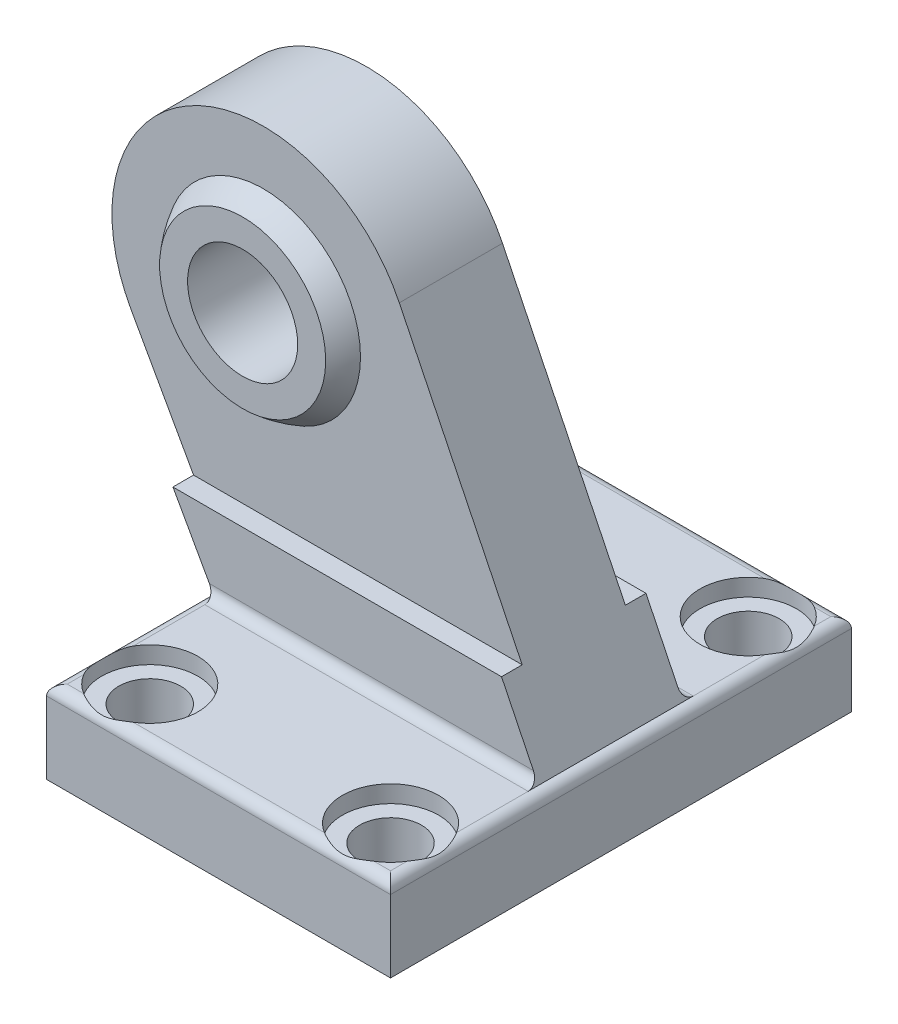
SolidWorks part; units mm, degrees
ref_plane "Front Plane" through (0, 0, 0) normal (0, 0, 1) x (1, 0, 0)
ref_plane "Top Plane" through (0, 0, 0) normal (0, 1, 0) x (1, 0, 0)
ref_plane "Right Plane" through (0, 0, 0) normal (1, 0, 0) x (0, 0, -1)
ref_plane "Plane1" through (0, 0, 0) normal (0, 0, 1) x (1, 0, 0)
sketch "Sketch1" plane through (0, 0, 0) normal (0, 0, 1) x (1, 0, 0)
  line L0 (-38.7147, 39.2858) -> (-23.5, 12)
  line L1 (-25, 10.5) -> (-25, 0)
  line L2 (-25, 0) -> (25, 0)
  line L3 (25, 0) -> (25, 10.5)
  line L4 (23.5, 12) -> (0.2753, 59.6404)
  arc A0 (0.2753, 59.6404) -> (-38.7147, 39.2858) centre (-19.5, 50) ccw
  arc A1 (-23.5, 12) -> (-25, 10.5) centre (-23.5, 10.5) ccw
  arc A2 (25, 10.5) -> (23.5, 12) centre (23.5, 10.5) ccw
extrude "Boss-Extrude1" add sketch "Sketch1" against normal blind 33.5 and the other way blind 33.5
ref_plane "Plane2" through (0, 0, 0) normal (1, 0, 0) x (0, 0, -1)
sketch "Sketch2" plane through (0, 0, 0) normal (1, 0, 0) x (0, 0, -1)
  line L0 (-67, 100) -> (-67, -1)
  line L1 (-67, -1) -> (-33.5, -1)
  line L2 (-33.5, -1) -> (-33.5, 10.5)
  line L3 (-32, 12) -> (-12, 12)
  line L4 (-10.5, 13.5) -> (-10.5, 23)
  line L5 (-10.5, 23) -> (-7.5, 23)
  line L6 (-7.5, 23) -> (-7.5, 73)
  line L7 (-7.5, 73) -> (7.5, 73)
  line L8 (7.5, 73) -> (7.5, 23)
  line L9 (7.5, 23) -> (10.5, 23)
  line L10 (10.5, 23) -> (10.5, 13.5)
  line L11 (12, 12) -> (32, 12)
  line L12 (33.5, 10.5) -> (33.5, -1)
  line L13 (33.5, -1) -> (67, -1)
  line L14 (67, -1) -> (67, 100)
  line L15 (67, 100) -> (-67, 100)
  arc A0 (-33.5, 10.5) -> (-32, 12) centre (-32, 10.5) cw
  arc A1 (-12, 12) -> (-10.5, 13.5) centre (-12, 13.5) ccw
  arc A2 (10.5, 13.5) -> (12, 12) centre (12, 13.5) ccw
  arc A3 (32, 12) -> (33.5, 10.5) centre (32, 10.5) cw
extrude "Cut-Extrude1" cut sketch "Sketch2" against normal blind 67 and the other way blind 67
ref_plane "Plane3" through (0, 50, 0) normal (0, 1, 0) x (1, 0, 0)
sketch "Sketch3" plane through (0, 50, 0) normal (0, 1, 0) x (1, 0, 0)
  line L0 (-19.5, 10.5) -> (-7.4273, 10.5)
  line L1 (-7.4273, -10.5) -> (-19.5, -10.5)
  line L2 (-19.5, -10.5) -> (-19.5, 10.5)
  line L3 (-19.5, -10.5) -> (-19.5, 10.5) construction
  arc A0 (-7.4273, 10.5) -> (-7.4273, -10.5) centre (-19.5, 0) cw
revolve "Revolve1" add sketch "Sketch3" angle 360 about L3
ref_plane "Plane4" through (0, 50, 0) normal (0, 1, 0) x (1, 0, 0)
sketch "Sketch4" plane through (0, 50, 0) normal (0, 1, 0) x (1, 0, 0)
  line L0 (-19.5, 16) -> (-11.5, 16)
  line L1 (-11.5, 16) -> (-11.5, -16)
  line L2 (-11.5, -16) -> (-19.5, -16)
  line L3 (-19.5, -16) -> (-19.5, 16)
  line L4 (-19.5, -16) -> (-19.5, 16) construction
revolve "Cut-Revolve1" cut sketch "Sketch4" angle 360 about L4
ref_plane "Plane5" through (0, 0, 26) normal (0, 0, 1) x (1, 0, 0)
sketch "Sketch5" plane through (0, 0, 26) normal (0, 0, 1) x (1, 0, 0)
  line L0 (17.5, 13) -> (24.5, 13)
  line L1 (24.5, 13) -> (24.5, 9.5)
  line L2 (24.5, 9.5) -> (22, 9.5)
  line L3 (22, 9.5) -> (22, -1)
  line L4 (22, -1) -> (17.5, -1)
  line L5 (17.5, -1) -> (17.5, 13)
  line L6 (17.5, -1) -> (17.5, 13) construction
revolve "Cut-Revolve2" cut sketch "Sketch5" angle 360 about L6
ref_plane "Plane6" through (0, 0, 26) normal (0, 0, 1) x (1, 0, 0)
sketch "Sketch6" plane through (0, 0, 26) normal (0, 0, 1) x (1, 0, 0)
  line L0 (-17.5, 13) -> (-10.5, 13)
  line L1 (-10.5, 13) -> (-10.5, 9.5)
  line L2 (-10.5, 9.5) -> (-13, 9.5)
  line L3 (-13, 9.5) -> (-13, -1)
  line L4 (-13, -1) -> (-17.5, -1)
  line L5 (-17.5, -1) -> (-17.5, 13)
  line L6 (-17.5, -1) -> (-17.5, 13) construction
revolve "Cut-Revolve3" cut sketch "Sketch6" angle 360 about L6
ref_plane "Plane7" through (0, 0, -26) normal (0, 0, 1) x (1, 0, 0)
sketch "Sketch7" plane through (0, 0, -26) normal (0, 0, 1) x (1, 0, 0)
  line L0 (-17.5, 13) -> (-10.5, 13)
  line L1 (-10.5, 13) -> (-10.5, 9.5)
  line L2 (-10.5, 9.5) -> (-13, 9.5)
  line L3 (-13, 9.5) -> (-13, -1)
  line L4 (-13, -1) -> (-17.5, -1)
  line L5 (-17.5, -1) -> (-17.5, 13)
  line L6 (-17.5, -1) -> (-17.5, 13) construction
revolve "Cut-Revolve4" cut sketch "Sketch7" angle 360 about L6
ref_plane "Plane8" through (0, 0, -26) normal (0, 0, 1) x (1, 0, 0)
sketch "Sketch8" plane through (0, 0, -26) normal (0, 0, 1) x (1, 0, 0)
  line L0 (17.5, 13) -> (24.5, 13)
  line L1 (24.5, 13) -> (24.5, 9.5)
  line L2 (24.5, 9.5) -> (22, 9.5)
  line L3 (22, 9.5) -> (22, -1)
  line L4 (22, -1) -> (17.5, -1)
  line L5 (17.5, -1) -> (17.5, 13)
  line L6 (17.5, -1) -> (17.5, 13) construction
revolve "Cut-Revolve5" cut sketch "Sketch8" angle 360 about L6
